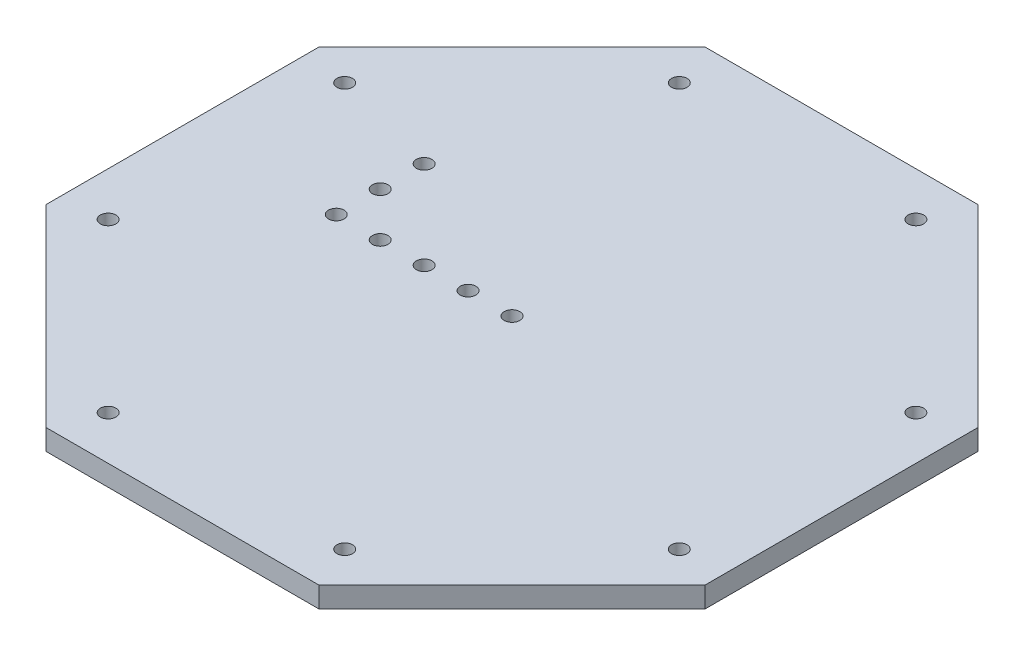
SolidWorks part; units mm, degrees
material "Custom Plastic"
ref_plane "Front Plane" through (0, 0, 0) normal (0, 0, 1) x (1, 0, 0)
ref_plane "Top Plane" through (0, 0, 0) normal (0, 1, 0) x (1, 0, 0)
ref_plane "Right Plane" through (0, 0, 0) normal (1, 0, 0) x (0, 0, -1)
ref_axis "Axis1" through (0, 6.2941, 0) along (0, -1, 0)
sketch "Sketch1" plane through (0, 0, 0) normal (0, 1, 0) x (1, 0, 0)
  line L1 (-39.4538, 95.25) -> (-95.25, 39.4538)
  line L2 (-95.25, 39.4538) -> (-95.25, -39.4538)
  line L3 (-95.25, -39.4538) -> (-39.4538, -95.25)
  line L4 (-39.4538, -95.25) -> (39.4538, -95.25)
  line L5 (39.4538, -95.25) -> (95.25, -39.4538)
  line L6 (95.25, -39.4538) -> (95.25, 39.4538)
  line L7 (95.25, 39.4538) -> (39.4538, 95.25)
  line L8 (39.4538, 95.25) -> (-39.4538, 95.25)
  circle A0 centre (0, 0) radius 95.25 construction
  dimension "D1" = 190.5
extrude "Base" add sketch "Sketch1" along normal blind 5.9944
sketch "Sketch2" plane through (0, 5.9944, 0) normal (0, 1, 0) x (1, 0, 0)
  line L0 (39.4538, 95.25) -> (-39.4538, 95.25) construction
  line L1 (34.1933, 82.55) -> (-34.1933, 82.55)
  line L2 (-34.1933, 82.55) -> (-82.55, 34.1933)
  line L3 (-82.55, 34.1933) -> (-82.55, -34.1933)
  line L4 (-82.55, -34.1933) -> (-34.1933, -82.55)
  line L5 (-34.1933, -82.55) -> (34.1933, -82.55)
  line L6 (34.1933, -82.55) -> (82.55, -34.1933)
  line L7 (82.55, -34.1933) -> (82.55, 34.1933)
  line L8 (82.55, 34.1933) -> (34.1933, 82.55)
  circle A0 centre (0, 0) radius 82.55 construction
  dimension "D1" = 12.7
hole_wizard "Mounting holes" positions "Sketch4" profile "Sketch3" hole size "#8" standard "ANSI Inch"
sketch "Sketch4" plane through (0, 5.9944, 0) normal (0, 1, 0) x (1, 0, 0)
  point P0 (-34.1933, 82.55)
  point P8 (34.1933, 82.55)
  point P11 (82.55, 34.1933)
  point P14 (82.55, -34.1933)
  point P17 (34.1933, -82.55)
  point P20 (-34.1933, -82.55)
  point P23 (-82.55, -34.1933)
  point P26 (-82.55, 34.1933)
sketch "Sketch3" plane through (-34.1933, 5.9944, -82.55) normal (1, 0, 0) x (0, 0, 1)
  line L0 (0, 0) -> (0, 5.9944)
  line L1 (0, 5.9944) -> (2.2479, 5.9944)
  line L2 (2.2479, 5.9944) -> (2.2479, 0)
  line L5 (2.2479, 0) -> (0, 0)
  line L10 (0, 5.9944) -> (-2.2479, 5.9944) construction
  line L11 (0, -6.35) -> (0, 107.95) construction
  dimension "Hole Dia." = 4.4958
  dimension "Hole Depth" = 5.9944
  dimension "Drill Angle" = 180
sketch "Sketch5" plane through (0, 5.9944, 0) normal (0, 1, 0) x (1, 0, 0)
  line L0 (0, 0) -> (-95.25, 0) construction
  line L1 (-95.25, 39.4538) -> (-95.25, -39.4538) construction
  line L2 (-50.8, 0) -> (-50.8, 25.4) construction
  point P4 (-12.7, 0)
  point P5 (-25.4, 0)
  point P7 (-38.1, 0)
  point P8 (-50.8, 0)
  point P11 (-50.8, 12.7)
  dimension "D1" = 12.7
  dimension "D2" = 12.7
  dimension "D3" = 12.7
  dimension "D4" = 12.7
  dimension "D5" = 25.4
hole_wizard "#8 Clearance Hole1" positions "Sketch7" profile "Sketch6" hole size "#8" standard "ANSI Inch" end condition through all
sketch "Sketch7" plane through (0, 5.9944, 0) normal (0, 1, 0) x (1, 0, 0)
  point P0 (0, 0)
  point P3 (-12.7, 0)
  point P6 (-25.4, 0)
  point P9 (-38.1, 0)
  point P12 (-50.8, 0)
  point P15 (-50.8, 12.7)
  point P18 (-50.8, 25.4)
sketch "Sketch6" plane through (0, 5.9944, 0) normal (1, 0, 0) x (0, 0, 1)
  line L0 (0, 0) -> (0, 5.9944)
  line L1 (0, 5.9944) -> (2.2479, 5.9944)
  line L2 (2.2479, 5.9944) -> (2.2479, 0)
  line L5 (2.2479, 0) -> (0, 0)
  line L11 (0, -6.35) -> (0, 107.95) construction
  dimension "Thru Hole Dia." = 4.4958
  dimension "Thru Hole Depth" = 5.9944
equation "\"MAT_THICKNESS\"=0.236"
equation "\"D1@Base\"=\"MAT_THICKNESS\""
